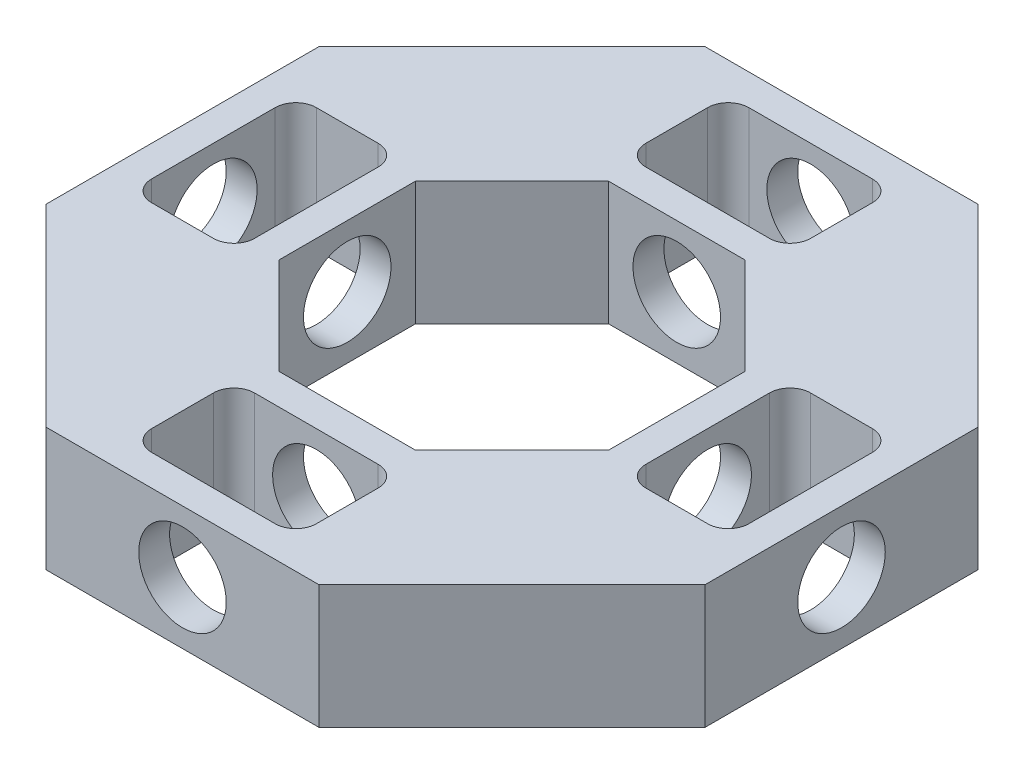
SolidWorks part; units mm, degrees
ref_plane "Front Plane" through (0, 0, 0) normal (0, 0, 1) x (1, 0, 0)
ref_plane "Top Plane" through (0, 0, 0) normal (0, 1, 0) x (1, 0, 0)
ref_plane "Right Plane" through (0, 0, 0) normal (1, 0, 0) x (0, 0, -1)
sketch "Sketch1" plane through (0, 0, 0) normal (0, 1, 0) x (1, 0, 0)
  line L0 (-50.8, -21.042) -> (-50.8, 21.042)
  line L1 (-50.8, 21.042) -> (-21.042, 50.8)
  line L2 (-21.042, 50.8) -> (21.042, 50.8)
  line L3 (21.042, 50.8) -> (50.8, 21.042)
  line L4 (50.8, 21.042) -> (50.8, -21.042)
  line L5 (50.8, -21.042) -> (21.042, -50.8)
  line L6 (21.042, -50.8) -> (-21.042, -50.8)
  line L7 (-21.042, -50.8) -> (-50.8, -21.042)
  line L8 (-25.4, 10.521) -> (-10.521, 25.4)
  line L9 (-10.521, 25.4) -> (10.521, 25.4)
  line L10 (10.521, 25.4) -> (25.4, 10.521)
  line L11 (25.4, 10.521) -> (25.4, -10.521)
  line L12 (25.4, -10.521) -> (10.521, -25.4)
  line L13 (10.521, -25.4) -> (-10.521, -25.4)
  line L14 (-10.521, -25.4) -> (-25.4, -10.521)
  line L15 (-25.4, -10.521) -> (-25.4, 10.521)
  point P2 (-28.7917, 9.5721)
  point P9 (50.8, 0)
  point P10 (-50.8, 0)
  point P12 (0, -50.8)
  point P13 (0, 50.8)
  point P22 (6.4819, -25.4)
  point P23 (-10.8534, -25.4)
  point P24 (14.019, 9.4214)
  point P25 (-3.3163, -3.2409)
  point P26 (0, 0)
  dimension "D1" = 25.4
  dimension "D2" = 25.4
  dimension "D3" = 25.4
  dimension "D4" = 25.4
  dimension "D5" = 25.4
  dimension "D6" = 25.4
  dimension "D7" = 25.4
  dimension "D8" = 25.4
  dimension "D9" = 50.8
  dimension "D10" = 50.8
  dimension "D11" = 50.8
  dimension "D12" = 50.8
  dimension "D13" = 50.8
extrude "Boss-Extrude1" add sketch "Sketch1" along normal blind 19.05
sketch "Sketch2" plane through (0, 19.05, 0) normal (0, 1, 0) x (1, 0, 0)
  line L0 (33.3375, 12.7) -> (42.8625, 12.7)
  line L1 (46.0375, 9.525) -> (46.0375, -9.525)
  line L2 (42.8625, -12.7) -> (33.3375, -12.7)
  line L3 (30.1625, -9.525) -> (30.1625, 9.525)
  line L5 (30.1625, 0) -> (46.0375, 0) construction
  arc A0 (46.0375, -9.525) -> (42.8625, -12.7) centre (42.8625, -9.525) cw
  arc A1 (33.3375, -12.7) -> (30.1625, -9.525) centre (33.3375, -9.525) cw
  arc A2 (42.8625, 12.7) -> (46.0375, 9.525) centre (42.8625, 9.525) cw
  arc A3 (33.3375, 12.7) -> (30.1625, 9.525) centre (33.3375, 9.525) ccw
  point P12 (30.1625, 0)
  point P16 (38.1, 0)
  dimension "D1" = 3.175
  dimension "D2" = 15.875
  dimension "D3" = 19.05
  dimension "D4" = 38.1
extrude "Cut-Extrude1" cut sketch "Sketch2" against normal through all
hole_wizard "1/2 Clearance Hole1" positions "Sketch3" profile "Sketch4" hole size "1/2" standard "ANSI Inch"
sketch "Sketch3" plane through (50.8, 0, 0) normal (1, 0, 0) x (0, 0, -1)
  line L0 (0, 0) -> (0, 19.05) construction
  line L1 (-21.042, 0) -> (21.042, 0) construction
  line L2 (-21.042, 19.05) -> (21.042, 19.05) construction
  point P0 (0, 9.525)
  point P12 (0, 9.525)
sketch "Sketch4" plane through (50.8, 9.525, 0) normal (0, 1, 0) x (0, 0, -1)
  line L0 (0, 0) -> (0, 67.5535)
  line L1 (0, 67.5535) -> (6.7462, 63.5)
  line L2 (6.7462, 63.5) -> (6.7462, 0)
  line L5 (6.7462, 0) -> (0, 0)
  line L10 (0, 67.5535) -> (-6.7462, 63.5) construction
  line L11 (0, -6.35) -> (0, 107.95) construction
  dimension "Hole Dia." = 13.4925
  dimension "Hole Depth" = 63.5
  dimension "Drill Angle" = 118
ref_axis "Axis1" through (0, -0.9525, 0) along (0, 1, 0)
pattern_circular "CirPattern1" count 4 over 360 about axis through (0, -0.9525, 0) along (0, 1, 0) of "Cut-Extrude1", "1/2 Clearance Hole1"
equation "\"D2@Sketch1\"=\"D1@Sketch1\""
equation "\"D3@Sketch1\"=\"D1@Sketch1\""
equation "\"D4@Sketch1\"=\"D1@Sketch1\""
equation "\"D5@Sketch1\"=\"D1@Sketch1\""
equation "\"D6@Sketch1\"=\"D1@Sketch1\""
equation "\"D7@Sketch1\"=\"D1@Sketch1\""
equation "\"D8@Sketch1\"=\"D1@Sketch1\""
equation "\"D10@Sketch1\"=\"D9@Sketch1\""
equation "\"D11@Sketch1\"=\"D9@Sketch1\""
equation "\"D12@Sketch1\"=\"D9@Sketch1\""
equation "\"D13@Sketch1\"=\"D9@Sketch1\""
